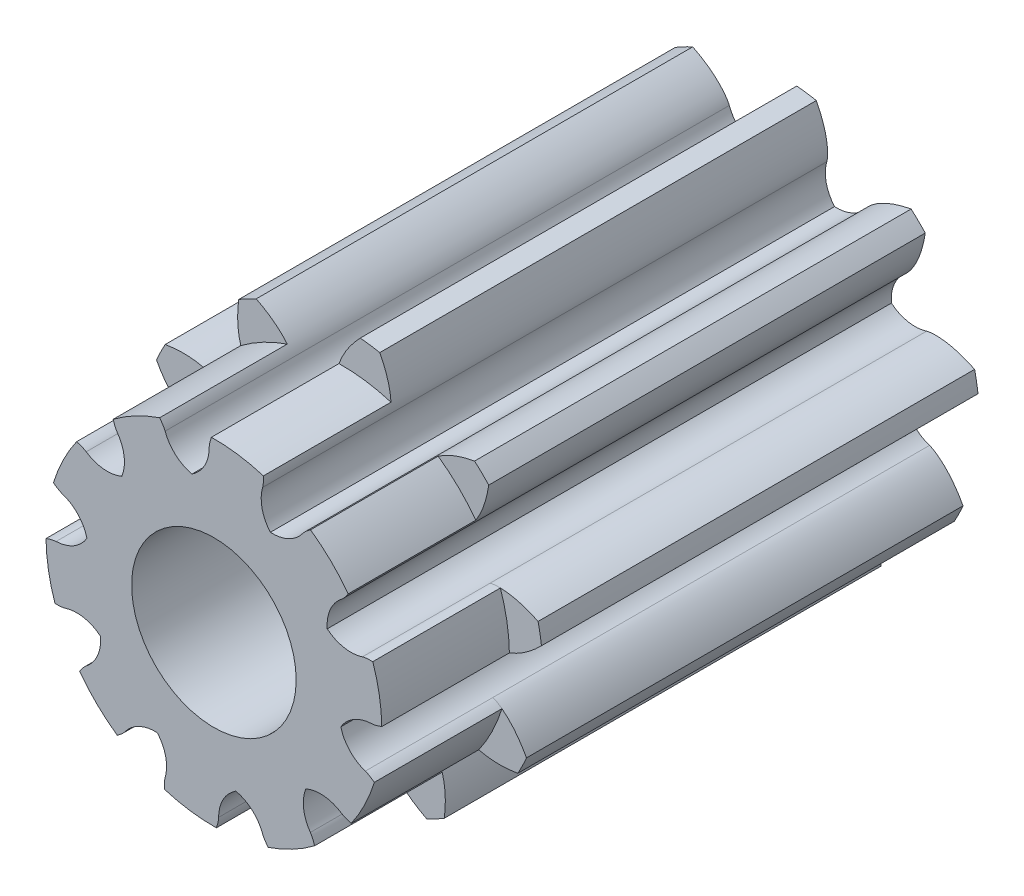
SolidWorks part; units mm, degrees
ref_plane "Front Plane" through (0, 0, 0) normal (0, 0, 1) x (1, 0, 0)
ref_plane "Top Plane" through (0, 0, 0) normal (0, 1, 0) x (1, 0, 0)
ref_plane "Right Plane" through (0, 0, 0) normal (1, 0, 0) x (0, 0, -1)
sketch "Sketch2" plane through (0, 0, 0) normal (0, 0, 1) x (1, 0, 0)
  spline S0 degree 4 poles (2.3492, 0) (2.3535, 0.0001) (2.3655, 0.001) (2.388, 0.0043) (2.4244, 0.0122) (2.4699, 0.0257) (2.5274, 0.0472) (2.5933, 0.0776) (2.6634, 0.116) (2.7368, 0.1632) (2.8072, 0.2147) (2.8746, 0.2702) (2.9391, 0.329) (3.0137, 0.4042) (3.0983, 0.4998) (3.1894, 0.6188) (3.2832, 0.7619) (3.368, 0.9153) (3.4422, 1.0722) (3.5063, 1.2365) (3.5603, 1.3995) (3.6047, 1.5733) (3.6397, 1.7361) (3.6656, 1.9222) (3.6825, 2.0736) (3.6905, 2.276) (3.6909, 2.3963) (3.6864, 2.5375) (3.6817, 2.6005) (3.679, 2.6392) knots 0 0 0 0 0 0.005377 0.015084 0.028532 0.04661 0.064855 0.092111 0.119476 0.146842 0.174209 0.201575 0.228941 0.256307 0.307035 0.361767 0.4165 0.471232 0.525964 0.580697 0.635429 0.690161 0.744894 0.799626 0.854358 0.909091 0.954545 1 1 1 1 1 construction
  spline S1 degree 4 poles (2.3492, 0) (2.3535, 0.0001) (2.3655, 0.001) (2.388, 0.0043) (2.4244, 0.0122) (2.4699, 0.0257) (2.5274, 0.0472) (2.5933, 0.0776) (2.6634, 0.116) (2.7368, 0.1632) (2.8072, 0.2147) (2.8746, 0.2702) (2.9391, 0.329) (3.0137, 0.4042) (3.0983, 0.4998) (3.1894, 0.6188) (3.2832, 0.7619) (3.368, 0.9153) (3.4422, 1.0722) (3.5063, 1.2365) (3.5603, 1.3995) (3.6047, 1.5733) (3.6397, 1.7361) (3.6656, 1.9222) (3.6825, 2.0736) (3.6888, 2.2322) (3.6902, 2.3096) (3.6902, 2.3492) knots 0 0 0 0 0 0.005377 0.015084 0.028532 0.04661 0.064855 0.092111 0.119476 0.146842 0.174209 0.201575 0.228941 0.256307 0.307035 0.361767 0.4165 0.471232 0.525964 0.580697 0.635429 0.690161 0.744894 0.799626 0.854358 0.909091 0.909091 0.909091 0.909091 0.909091
sketch "Sketch3" plane through (0, 0, 0) normal (0, 0, 1) x (1, 0, 0)
  line L0 (0, 0) -> (4.3237, 0) construction
  line L1 (3.6796, 0) -> (-3.6796, 0) construction
  line L2 (0, 0) -> (4.6983, 0.8161) construction
  circle A0 centre (0, 0) radius 2.3492 construction
  circle A1 centre (0, 0) radius 2.5 construction
  circle A2 centre (0, 0) radius 1.875
  circle A3 centre (0, 0) radius 3
  arc A4 (2.3492, 0) -> (1.8252, -0.4294) centre (2.3678, -0.5571) ccw
  arc A5 (2.2116, 0.7922) -> (1.5734, 1.0198) centre (2.0412, 1.323) cw
  spline S0 degree 4 poles (1.2598, 2999.6445) (0.5098, 35.997) (1.2863, 0.522) (1.9195, -0.0971) (2.4244, 0.0122) (2.4699, 0.0257) (2.5274, 0.0472) (2.5933, 0.0776) (2.6634, 0.116) (2.7368, 0.1632) (2.8072, 0.2147) (2.8746, 0.2702) (2.9391, 0.329) (3.0137, 0.4042) (3.0983, 0.4998) (3.1894, 0.6188) (3.2832, 0.7619) (3.368, 0.9153) (3.4422, 1.0722) (3.5063, 1.2365) (3.5603, 1.3995) (3.6047, 1.5733) (3.6397, 1.7361) (3.6656, 1.9222) (3.7713, 2.8662) (3.4608, 6.6353) (2.9119, -59.9143) (2.2294, 3002.2795) knots -0.601208 -0.601208 -0.601208 -0.601208 -0.601208 0.005377 0.015084 0.028532 0.04661 0.064855 0.092111 0.119476 0.146842 0.174209 0.201575 0.228941 0.256307 0.307035 0.361767 0.4165 0.471232 0.525964 0.580697 0.635429 0.690161 0.744894 0.799626 0.854358 2.055109 2.055109 2.055109 2.055109 2.055109 only from (2.3492, 0) to (3.6902, 2.3492) construction
  spline S1 degree 4 poles (2.3492, 0) (2.3535, 0.0001) (2.3655, 0.001) (2.388, 0.0043) (2.4244, 0.0122) (2.4699, 0.0257) (2.5274, 0.0472) (2.5933, 0.0776) (2.6634, 0.116) (2.7368, 0.1632) (2.8072, 0.2147) (2.8768, 0.272) (2.927, 0.318) (2.9601, 0.3506) (2.9773, 0.3681) knots 0 0 0 0 0 0.005377 0.015084 0.028532 0.04661 0.064855 0.092111 0.119476 0.146842 0.174209 0.201575 0.232398 0.232398 0.232398 0.232398 0.232398
  spline S2 degree 4 poles (2.2116, 0.7922) (2.2157, 0.7935) (2.2273, 0.7968) (2.2496, 0.8013) (2.2865, 0.8061) (2.3339, 0.8087) (2.3953, 0.8078) (2.4676, 0.8015) (2.5465, 0.7889) (2.6315, 0.7693) (2.7152, 0.7445) (2.8, 0.7141) (2.8628, 0.6877) (2.9049, 0.6682) (2.9271, 0.6575) knots 0 0 0 0 0 0.005377 0.015084 0.028532 0.04661 0.064855 0.092111 0.119476 0.146842 0.174209 0.201575 0.232398 0.232398 0.232398 0.232398 0.232398
  point P15 (2.4631, 0.4278)
  point P16 (2.4997, 0.0373)
  dimension "D1" = 6
  dimension "D2" = 3.75
  dimension "D3" = 5
  dimension "D4" = 4.6985
  dimension "D5" = 0.3927
extrude "Boss-Extrude1" add sketch "Sketch3" along normal blind 6.5 contours A2 region at (0, 0, 0)
extrude "Boss-Extrude2" add sketch "Sketch3<3>" along normal up to surface (6.5 mm away) contours S2 A5 A2 A4 S1 A3 region at (2.3064, 0.4006, 0) up to face at (1.875, 0, 6.5)
sketch "Sketch3<3>" plane through (0, 0, 0) normal (0, 0, 1) x (1, 0, 0) same geometry as "Sketch3"
pattern_circular "CirPattern1" count 10 over 360 about axis through (0, 0, 6.5) along (0, 0, -1) of "Boss-Extrude2"
sketch "Sketch4" plane through (0, 0, 6.5) normal (0, 0, 1) x (1, 0, 0)
  circle A0 centre (0, 0) radius 1.225
  dimension "D1" = 2.45
extrude "Cut-Extrude1" cut sketch "Sketch4" against normal blind 6.5
sketch "Sketch5" plane through (0, 0, 6.5) normal (0, 0, 1) x (1, 0, 0)
  circle A0 centre (0, 0) radius 1.225 construction
  circle A1 centre (0, 0) radius 1.225
  arc A2 (-0.8079, 2.3659) -> (-1.4994, 2.0004) centre (0, 0) ccw
  arc A3 (-2.0442, 1.4392) -> (-2.3889, 0.737) centre (0, 0) ccw
  arc A4 (-2.4997, -0.0373) -> (-2.3659, -0.8079) centre (0, 0) ccw
  arc A5 (-2.0004, -1.4994) -> (-1.4392, -2.0442) centre (0, 0) ccw
  arc A6 (-0.737, -2.3889) -> (0.0373, -2.4997) centre (0, 0) ccw
  arc A7 (0.8079, -2.3659) -> (1.4994, -2.0004) centre (0, 0) ccw
  arc A8 (2.0442, -1.4392) -> (2.3889, -0.737) centre (0, 0) ccw
  arc A9 (2.4997, 0.0373) -> (2.3659, 0.8079) centre (0, 0) ccw
  arc A10 (2.0004, 1.4994) -> (1.4392, 2.0442) centre (0, 0) ccw
  arc A11 (0.737, 2.3889) -> (-0.0373, 2.4997) centre (0, 0) ccw
  arc A30 (1.8897, -0.2705) -> (2.2549, -0.659) centre (2.429, -0.1295) ccw
  arc A31 (2.3492, 0) -> (1.8897, -0.2705) centre (2.3678, -0.5571) ccw
  arc A32 (2.9773, 0.3681) -> (2.9271, 0.6575) centre (0, 0) ccw
  arc A33 (1.6878, 0.8919) -> (2.2116, 0.7922) centre (2.0412, 1.323) ccw
  arc A34 (1.9006, 1.3808) -> (1.6878, 0.8919) centre (2.243, 0.941) ccw
  arc A35 (2.1923, 2.0478) -> (1.9816, 2.2524) centre (0, 0) ccw
  arc A36 (0.8412, 1.7136) -> (1.3236, 1.9409) centre (0.8737, 2.2701) ccw
  arc A37 (0.726, 2.2343) -> (0.8412, 1.7136) centre (1.2615, 2.0797) ccw
  arc A38 (0.57, 2.9454) -> (0.2792, 2.987) centre (0, 0) ccw
  arc A39 (-0.3267, 1.8808) -> (-0.07, 2.3482) centre (-0.6274, 2.3501) ccw
  arc A40 (-0.726, 2.2343) -> (-0.3267, 1.8808) centre (-0.2018, 2.424) ccw
  arc A41 (-1.2701, 2.7179) -> (-1.5298, 2.5806) centre (0, 0) ccw
  arc A42 (-1.3698, 1.3296) -> (-1.4369, 1.8586) centre (-1.889, 1.5325) ccw
  arc A43 (-1.9006, 1.3808) -> (-1.3698, 1.3296) centre (-1.5881, 1.8424) ccw
  arc A44 (-2.6251, 1.4522) -> (-2.7545, 1.1886) centre (0, 0) ccw
  arc A45 (-1.8897, 0.2705) -> (-2.2549, 0.659) centre (-2.429, 0.1295) ccw
  arc A46 (-2.3492, 0) -> (-1.8897, 0.2705) centre (-2.3678, 0.5571) ccw
  arc A47 (-2.9773, -0.3681) -> (-2.9271, -0.6575) centre (0, 0) ccw
  arc A48 (-1.6878, -0.8919) -> (-2.2116, -0.7922) centre (-2.0412, -1.323) ccw
  arc A49 (-1.9006, -1.3808) -> (-1.6878, -0.8919) centre (-2.243, -0.941) ccw
  arc A50 (-2.1923, -2.0478) -> (-1.9816, -2.2524) centre (0, 0) ccw
  arc A51 (-0.8412, -1.7136) -> (-1.3236, -1.9409) centre (-0.8737, -2.2701) ccw
  arc A52 (-0.726, -2.2343) -> (-0.8412, -1.7136) centre (-1.2615, -2.0797) ccw
  arc A53 (-0.57, -2.9454) -> (-0.2792, -2.987) centre (0, 0) ccw
  arc A54 (0.3267, -1.8808) -> (0.07, -2.3482) centre (0.6274, -2.3501) ccw
  arc A55 (0.726, -2.2343) -> (0.3267, -1.8808) centre (0.2018, -2.424) ccw
  arc A56 (1.2701, -2.7179) -> (1.5298, -2.5806) centre (0, 0) ccw
  arc A57 (1.3698, -1.3296) -> (1.4369, -1.8586) centre (1.889, -1.5325) ccw
  arc A58 (1.9006, -1.3808) -> (1.3698, -1.3296) centre (1.5881, -1.8424) ccw
  arc A59 (2.6251, -1.4522) -> (2.7545, -1.1886) centre (0, 0) ccw
  arc A60 (1.8897, -0.2705) -> (2.2549, -0.659) centre (2.429, -0.1295) ccw
  arc A61 (2.3492, 0) -> (1.8897, -0.2705) centre (2.3678, -0.5571) ccw
  arc A63 (1.6878, 0.8919) -> (2.2116, 0.7922) centre (2.0412, 1.323) ccw
  arc A64 (1.9006, 1.3808) -> (1.6878, 0.8919) centre (2.243, 0.941) ccw
  arc A66 (0.8412, 1.7136) -> (1.3236, 1.9409) centre (0.8737, 2.2701) ccw
  arc A67 (0.726, 2.2343) -> (0.8412, 1.7136) centre (1.2615, 2.0797) ccw
  arc A69 (-0.3267, 1.8808) -> (-0.07, 2.3482) centre (-0.6274, 2.3501) ccw
  arc A70 (-0.726, 2.2343) -> (-0.3267, 1.8808) centre (-0.2018, 2.424) ccw
  arc A72 (-1.3698, 1.3296) -> (-1.4369, 1.8586) centre (-1.889, 1.5325) ccw
  arc A73 (-1.9006, 1.3808) -> (-1.3698, 1.3296) centre (-1.5881, 1.8424) ccw
  arc A75 (-1.8897, 0.2705) -> (-2.2549, 0.659) centre (-2.429, 0.1295) ccw
  arc A76 (-2.3492, 0) -> (-1.8897, 0.2705) centre (-2.3678, 0.5571) ccw
  arc A78 (-1.6878, -0.8919) -> (-2.2116, -0.7922) centre (-2.0412, -1.323) ccw
  arc A79 (-1.9006, -1.3808) -> (-1.6878, -0.8919) centre (-2.243, -0.941) ccw
  arc A81 (-0.8412, -1.7136) -> (-1.3236, -1.9409) centre (-0.8737, -2.2701) ccw
  arc A82 (-0.726, -2.2343) -> (-0.8412, -1.7136) centre (-1.2615, -2.0797) ccw
  arc A84 (0.3267, -1.8808) -> (0.07, -2.3482) centre (0.6274, -2.3501) ccw
  arc A85 (0.726, -2.2343) -> (0.3267, -1.8808) centre (0.2018, -2.424) ccw
  arc A87 (1.3698, -1.3296) -> (1.4369, -1.8586) centre (1.889, -1.5325) ccw
  arc A88 (1.9006, -1.3808) -> (1.3698, -1.3296) centre (1.5881, -1.8424) ccw
  spline S20 degree 4 poles (1.2598, 2999.7738) (0.5098, 35.9981) (1.2863, 0.522) (1.9194, -0.0971) (2.4244, 0.0122) (2.4699, 0.0257) (2.5274, 0.0472) (2.5933, 0.0776) (2.6634, 0.116) (2.7368, 0.1632) (2.8072, 0.2147) (4.8119, 1.8647) (3.3546, 7.3675) (1.052, 5.6298) (-1.6472, -2999.6052) knots -0.601214 -0.601214 -0.601214 -0.601214 -0.601214 0.005377 0.015084 0.028532 0.04661 0.064855 0.092111 0.119476 0.146842 0.174209 0.201575 3.374744 3.374744 3.374744 3.374744 3.374744 only from (2.3492, 0) to (2.9773, 0.3681)
  spline S21 degree 4 poles (-1013.0696, 2823.2643) (2.8889, -4.9453) (5.6426, -5.8046) (5.1589, -0.1327) (2.7152, 0.7445) (2.6315, 0.7693) (2.5465, 0.7889) (2.4676, 0.8015) (2.3953, 0.8078) (2.3339, 0.8087) (2.2865, 0.8061) (1.7743, 0.7387) (1.387, -0.0576) (12.6186, -33.7149) (1012.6847, -2823.3385) knots -3.142323 -3.142323 -3.142323 -3.142323 -3.142323 0.030823 0.05819 0.085556 0.112922 0.140288 0.167544 0.185788 0.203867 0.217315 0.227022 0.833597 0.833597 0.833597 0.833597 0.833597 only from (2.9271, 0.6575) to (2.2116, 0.7922)
  spline S22 degree 4 poles (-1762.2036, 2427.6085) (-20.7467, 29.4227) (0.7338, 1.1784) (1.6099, 1.0497) (1.9542, 1.4349) (1.983, 1.4726) (2.0169, 1.5238) (2.0524, 1.5871) (2.0865, 1.6594) (2.1182, 1.7406) (2.1449, 1.8238) (2.7969, 4.3369) (-1.6166, 7.9322) (-2.458, 5.173) (1761.7911, -2427.6998) knots -0.601214 -0.601214 -0.601214 -0.601214 -0.601214 0.005377 0.015084 0.028532 0.04661 0.064855 0.092111 0.119476 0.146842 0.174209 0.201575 3.374744 3.374744 3.374744 3.374744 3.374744 only from (1.9006, 1.3808) to (2.1923, 2.0478)
  spline S23 degree 4 poles (-2479.0637, 1688.6014) (5.244, -2.3027) (7.9768, -1.3794) (4.2516, 2.9249) (1.759, 2.1983) (1.6767, 2.1692) (1.5964, 2.1351) (1.5252, 2.0988) (1.463, 2.0615) (1.4128, 2.026) (1.376, 1.9961) (1.0012, 1.6405) (1.156, 0.7686) (30.0258, -19.8589) (2478.7959, -1688.8877) knots -3.142323 -3.142323 -3.142323 -3.142323 -3.142323 0.030823 0.05819 0.085556 0.112922 0.140288 0.167544 0.185788 0.203867 0.217315 0.227022 0.833597 0.833597 0.833597 0.833597 0.833597 only from (1.9816, 2.2524) to (1.3236, 1.9409)
  spline S24 degree 4 poles (-2852.5651, 928.1792) (-34.0787, 11.6089) (-0.099, 1.3847) (0.6855, 1.7955) (0.7376, 2.3095) (0.7388, 2.3569) (0.7361, 2.4183) (0.7276, 2.4903) (0.7127, 2.5689) (0.6905, 2.6533) (0.6633, 2.7362) (-0.2864, 5.1527) (-5.9703, 5.467) (-5.0292, 2.7402) (2852.2851, -928.4956) knots -0.601214 -0.601214 -0.601214 -0.601214 -0.601214 0.005377 0.015084 0.028532 0.04661 0.064855 0.092111 0.119476 0.146842 0.174209 0.201575 3.374744 3.374744 3.374744 3.374744 3.374744 only from (0.726, 2.2343) to (0.57, 2.9454)
  spline S25 degree 4 poles (-2998.1397, -91.0498) (5.596, 1.2194) (7.2641, 3.5727) (1.7204, 4.8654) (0.131, 2.8124) (0.0815, 2.7404) (0.0366, 2.6657) (0.0002, 2.5945) (-0.0281, 2.5277) (-0.0479, 2.4695) (-0.0601, 2.4237) (-0.1543, 1.9157) (0.4834, 1.3013) (35.9641, 1.5825) (2998.0912, 90.6608) knots -3.142323 -3.142323 -3.142323 -3.142323 -3.142323 0.030823 0.05819 0.085556 0.112922 0.140288 0.167544 0.185788 0.203867 0.217315 0.227022 0.833597 0.833597 0.833597 0.833597 0.833597 only from (0.2792, 2.987) to (-0.07, 2.3482)
  spline S26 degree 4 poles (-2853.3437, -925.7829) (-34.3938, -10.6392) (-0.894, 1.062) (-0.5008, 1.8555) (-0.7607, 2.302) (-0.7877, 2.341) (-0.8259, 2.3891) (-0.8752, 2.4424) (-0.9334, 2.4972) (-1.0009, 2.5524) (-1.0717, 2.6035) (-3.2604, 4.0002) (-8.0435, 0.9137) (-5.6793, -0.7392) (2853.3031, 925.3624) knots -0.601214 -0.601214 -0.601214 -0.601214 -0.601214 0.005377 0.015084 0.028532 0.04661 0.064855 0.092111 0.119476 0.146842 0.174209 0.201575 3.374744 3.374744 3.374744 3.374744 3.374744 only from (-0.726, 2.2343) to (-1.2701, 2.7179)
  spline S27 degree 4 poles (-2372.0282, -1835.9231) (3.8105, 4.2757) (3.7768, 7.1601) (-1.468, 4.9474) (-1.5471, 2.3522) (-1.5448, 2.265) (-1.5372, 2.1781) (-1.5248, 2.0991) (-1.5085, 2.0284) (-1.4903, 1.9697) (-1.4732, 1.9255) (-1.2508, 1.4592) (-0.3738, 1.3369) (28.1654, 22.4195) (2372.2177, 1835.58) knots -3.142323 -3.142323 -3.142323 -3.142323 -3.142323 0.030823 0.05819 0.085556 0.112922 0.140288 0.167544 0.185788 0.203867 0.217315 0.227022 0.833597 0.833597 0.833597 0.833597 0.833597 only from (-1.5298, 2.5806) to (-1.4369, 1.8586)
  spline S28 degree 4 poles (-1764.242, -2426.1275) (-21.5716, -28.8234) (-1.3475, 0.3337) (-1.4958, 1.2068) (-1.9685, 1.4152) (-2.0133, 1.4309) (-2.0725, 1.4474) (-2.1436, 1.4615) (-2.2229, 1.4716) (-2.31, 1.4766) (-2.3973, 1.4763) (-4.989, 1.3198) (-7.0444, -3.9887) (-4.1602, -3.9363) (1764.4563, 2425.7634) knots -0.601214 -0.601214 -0.601214 -0.601214 -0.601214 0.005377 0.015084 0.028532 0.04661 0.064855 0.092111 0.119476 0.146842 0.174209 0.201575 3.374744 3.374744 3.374744 3.374744 3.374744 only from (-1.9006, 1.3808) to (-2.6251, 1.4522)
  spline S29 degree 4 poles (-839.8826, -2879.5362) (0.5696, 5.6989) (-1.1531, 8.0126) (-4.0956, 3.1397) (-2.6343, 0.9936) (-2.5811, 0.9244) (-2.5239, 0.8585) (-2.4674, 0.802) (-2.4127, 0.7544) (-2.3635, 0.7176) (-2.3236, 0.6918) (-1.8696, 0.4453) (-1.0882, 0.8619) (9.6085, 34.693) (840.2376, 2879.3699) knots -3.142323 -3.142323 -3.142323 -3.142323 -3.142323 0.030823 0.05819 0.085556 0.112922 0.140288 0.167544 0.185788 0.203867 0.217315 0.227022 0.833597 0.833597 0.833597 0.833597 0.833597 only from (-2.7545, 1.1886) to (-2.2549, 0.659)
  spline S30 degree 4 poles (-1.2598, -2999.7738) (-0.5098, -35.9981) (-1.2863, -0.522) (-1.9194, 0.0971) (-2.4244, -0.0122) (-2.4699, -0.0257) (-2.5274, -0.0472) (-2.5933, -0.0776) (-2.6634, -0.116) (-2.7368, -0.1632) (-2.8072, -0.2147) (-4.8119, -1.8647) (-3.3546, -7.3675) (-1.052, -5.6298) (1.6472, 2999.6052) knots -0.601214 -0.601214 -0.601214 -0.601214 -0.601214 0.005377 0.015084 0.028532 0.04661 0.064855 0.092111 0.119476 0.146842 0.174209 0.201575 3.374744 3.374744 3.374744 3.374744 3.374744 only from (-2.3492, 0) to (-2.9773, -0.3681)
  spline S31 degree 4 poles (1013.0696, -2823.2643) (-2.8889, 4.9453) (-5.6426, 5.8046) (-5.1589, 0.1327) (-2.7152, -0.7445) (-2.6315, -0.7693) (-2.5465, -0.7889) (-2.4676, -0.8015) (-2.3953, -0.8078) (-2.3339, -0.8087) (-2.2865, -0.8061) (-1.7743, -0.7387) (-1.387, 0.0576) (-12.6186, 33.7149) (-1012.6847, 2823.3385) knots -3.142323 -3.142323 -3.142323 -3.142323 -3.142323 0.030823 0.05819 0.085556 0.112922 0.140288 0.167544 0.185788 0.203867 0.217315 0.227022 0.833597 0.833597 0.833597 0.833597 0.833597 only from (-2.9271, -0.6575) to (-2.2116, -0.7922)
  spline S32 degree 4 poles (1762.2036, -2427.6085) (20.7467, -29.4227) (-0.7338, -1.1784) (-1.6099, -1.0497) (-1.9542, -1.4349) (-1.983, -1.4726) (-2.0169, -1.5238) (-2.0524, -1.5871) (-2.0865, -1.6594) (-2.1182, -1.7406) (-2.1449, -1.8238) (-2.7969, -4.3369) (1.6166, -7.9322) (2.458, -5.173) (-1761.7911, 2427.6998) knots -0.601214 -0.601214 -0.601214 -0.601214 -0.601214 0.005377 0.015084 0.028532 0.04661 0.064855 0.092111 0.119476 0.146842 0.174209 0.201575 3.374744 3.374744 3.374744 3.374744 3.374744 only from (-1.9006, -1.3808) to (-2.1923, -2.0478)
  spline S33 degree 4 poles (2479.0637, -1688.6014) (-5.244, 2.3027) (-7.9768, 1.3794) (-4.2516, -2.9249) (-1.759, -2.1983) (-1.6767, -2.1692) (-1.5964, -2.1351) (-1.5252, -2.0988) (-1.463, -2.0615) (-1.4128, -2.026) (-1.376, -1.9961) (-1.0012, -1.6405) (-1.156, -0.7686) (-30.0258, 19.8589) (-2478.7959, 1688.8877) knots -3.142323 -3.142323 -3.142323 -3.142323 -3.142323 0.030823 0.05819 0.085556 0.112922 0.140288 0.167544 0.185788 0.203867 0.217315 0.227022 0.833597 0.833597 0.833597 0.833597 0.833597 only from (-1.9816, -2.2524) to (-1.3236, -1.9409)
  spline S34 degree 4 poles (2852.5651, -928.1792) (34.0787, -11.6089) (0.099, -1.3847) (-0.6855, -1.7955) (-0.7376, -2.3095) (-0.7388, -2.3569) (-0.7361, -2.4183) (-0.7276, -2.4903) (-0.7127, -2.5689) (-0.6905, -2.6533) (-0.6633, -2.7362) (0.2864, -5.1527) (5.9703, -5.467) (5.0292, -2.7402) (-2852.2851, 928.4955) knots -0.601214 -0.601214 -0.601214 -0.601214 -0.601214 0.005377 0.015084 0.028532 0.04661 0.064855 0.092111 0.119476 0.146842 0.174209 0.201575 3.374744 3.374744 3.374744 3.374744 3.374744 only from (-0.726, -2.2343) to (-0.57, -2.9454)
  spline S35 degree 4 poles (2998.1397, 91.0498) (-5.596, -1.2194) (-7.2641, -3.5727) (-1.7204, -4.8654) (-0.131, -2.8124) (-0.0815, -2.7404) (-0.0366, -2.6657) (-0.0002, -2.5945) (0.0281, -2.5277) (0.0479, -2.4695) (0.0601, -2.4237) (0.1543, -1.9157) (-0.4834, -1.3013) (-35.9641, -1.5825) (-2998.0912, -90.6608) knots -3.142323 -3.142323 -3.142323 -3.142323 -3.142323 0.030823 0.05819 0.085556 0.112922 0.140288 0.167544 0.185788 0.203867 0.217315 0.227022 0.833597 0.833597 0.833597 0.833597 0.833597 only from (-0.2792, -2.987) to (0.07, -2.3482)
  spline S36 degree 4 poles (2853.3437, 925.7829) (34.3938, 10.6392) (0.894, -1.062) (0.5008, -1.8555) (0.7607, -2.302) (0.7877, -2.341) (0.8259, -2.3891) (0.8752, -2.4424) (0.9334, -2.4972) (1.0009, -2.5524) (1.0717, -2.6035) (3.2604, -4.0002) (8.0435, -0.9137) (5.6793, 0.7392) (-2853.3031, -925.3624) knots -0.601214 -0.601214 -0.601214 -0.601214 -0.601214 0.005377 0.015084 0.028532 0.04661 0.064855 0.092111 0.119476 0.146842 0.174209 0.201575 3.374744 3.374744 3.374744 3.374744 3.374744 only from (0.726, -2.2343) to (1.2701, -2.7179)
  spline S37 degree 4 poles (2372.0282, 1835.9231) (-3.8105, -4.2757) (-3.7768, -7.1601) (1.468, -4.9474) (1.5471, -2.3522) (1.5448, -2.265) (1.5372, -2.1781) (1.5248, -2.0991) (1.5085, -2.0284) (1.4903, -1.9697) (1.4732, -1.9255) (1.2508, -1.4592) (0.3738, -1.3369) (-28.1654, -22.4195) (-2372.2177, -1835.58) knots -3.142323 -3.142323 -3.142323 -3.142323 -3.142323 0.030823 0.05819 0.085556 0.112922 0.140288 0.167544 0.185788 0.203867 0.217315 0.227022 0.833597 0.833597 0.833597 0.833597 0.833597 only from (1.5298, -2.5806) to (1.4369, -1.8586)
  spline S38 degree 4 poles (1764.242, 2426.1275) (21.5716, 28.8234) (1.3475, -0.3337) (1.4958, -1.2068) (1.9685, -1.4152) (2.0133, -1.4309) (2.0725, -1.4474) (2.1436, -1.4615) (2.2229, -1.4716) (2.31, -1.4766) (2.3973, -1.4763) (4.989, -1.3198) (7.0444, 3.9887) (4.1602, 3.9363) (-1764.4563, -2425.7634) knots -0.601214 -0.601214 -0.601214 -0.601214 -0.601214 0.005377 0.015084 0.028532 0.04661 0.064855 0.092111 0.119476 0.146842 0.174209 0.201575 3.374744 3.374744 3.374744 3.374744 3.374744 only from (1.9006, -1.3808) to (2.6251, -1.4522)
  spline S39 degree 4 poles (839.8826, 2879.5362) (-0.5696, -5.6989) (1.1531, -8.0126) (4.0956, -3.1397) (2.6343, -0.9936) (2.5811, -0.9244) (2.5239, -0.8585) (2.4674, -0.802) (2.4127, -0.7544) (2.3635, -0.7176) (2.3236, -0.6918) (1.8696, -0.4453) (1.0882, -0.8619) (-9.6085, -34.693) (-840.2376, -2879.3699) knots -3.142323 -3.142323 -3.142323 -3.142323 -3.142323 0.030823 0.05819 0.085556 0.112922 0.140288 0.167544 0.185788 0.203867 0.217315 0.227022 0.833597 0.833597 0.833597 0.833597 0.833597 only from (2.7545, -1.1886) to (2.2549, -0.659)
  spline S40 degree 4 poles (2.3492, 0) (2.3535, 0.0001) (2.3655, 0.001) (2.388, 0.0043) (2.4261, 0.0125) (2.4593, 0.0226) (2.4846, 0.0315) (2.4997, 0.0373) knots 0 0 0 0 0 0.005377 0.015084 0.028532 0.048809 0.048809 0.048809 0.048809 0.048809
  spline S41 degree 4 poles (2.3659, 0.8079) (2.3497, 0.8082) (2.3228, 0.8081) (2.2882, 0.8063) (2.2496, 0.8013) (2.2273, 0.7968) (2.2157, 0.7935) (2.2116, 0.7922) knots 0.18359 0.18359 0.18359 0.18359 0.18359 0.203867 0.217315 0.227022 0.232398 0.232398 0.232398 0.232398 0.232398
  spline S42 degree 4 poles (1.9006, 1.3808) (1.904, 1.3835) (1.9132, 1.3912) (1.9294, 1.4071) (1.9554, 1.4362) (1.9763, 1.4638) (1.9916, 1.4859) (2.0004, 1.4994) knots 0 0 0 0 0 0.005377 0.015084 0.028532 0.048809 0.048809 0.048809 0.048809 0.048809
  spline S43 degree 4 poles (1.4392, 2.0442) (1.4259, 2.035) (1.4042, 2.0191) (1.3772, 1.9973) (1.349, 1.9705) (1.3336, 1.9538) (1.3261, 1.9443) (1.3236, 1.9409) knots 0.18359 0.18359 0.18359 0.18359 0.18359 0.203867 0.217315 0.227022 0.232398 0.232398 0.232398 0.232398 0.232398
  spline S44 degree 4 poles (0.726, 2.2343) (0.7271, 2.2384) (0.73, 2.25) (0.7338, 2.2725) (0.7378, 2.3112) (0.7385, 2.3459) (0.7378, 2.3728) (0.737, 2.3889) knots 0 0 0 0 0 0.005377 0.015084 0.028532 0.048809 0.048809 0.048809 0.048809 0.048809
  spline S45 degree 4 poles (-0.0373, 2.4997) (-0.0426, 2.4845) (-0.0507, 2.4588) (-0.0598, 2.4254) (-0.0669, 2.3871) (-0.0695, 2.3645) (-0.07, 2.3525) (-0.07, 2.3482) knots 0.18359 0.18359 0.18359 0.18359 0.18359 0.203867 0.217315 0.227022 0.232398 0.232398 0.232398 0.232398 0.232398
  spline S46 degree 4 poles (-0.726, 2.2343) (-0.7274, 2.2383) (-0.7319, 2.2494) (-0.742, 2.2698) (-0.7616, 2.3035) (-0.7814, 2.3319) (-0.7978, 2.3533) (-0.8079, 2.3659) knots 0 0 0 0 0 0.005377 0.015084 0.028532 0.048809 0.048809 0.048809 0.048809 0.048809
  spline S47 degree 4 poles (-1.4994, 2.0004) (-1.4948, 1.985) (-1.4863, 1.9594) (-1.474, 1.927) (-1.4572, 1.8919) (-1.4461, 1.872) (-1.4394, 1.862) (-1.4369, 1.8586) knots 0.18359 0.18359 0.18359 0.18359 0.18359 0.203867 0.217315 0.227022 0.232398 0.232398 0.232398 0.232398 0.232398
  spline S48 degree 4 poles (-1.9006, 1.3808) (-1.9041, 1.3832) (-1.9143, 1.3896) (-1.9345, 1.4002) (-1.9701, 1.4159) (-2.0029, 1.4273) (-2.0286, 1.4349) (-2.0442, 1.4392) knots 0 0 0 0 0 0.005377 0.015084 0.028532 0.048809 0.048809 0.048809 0.048809 0.048809
  spline S49 degree 4 poles (-2.3889, 0.737) (-2.376, 0.7273) (-2.3542, 0.7116) (-2.3251, 0.6926) (-2.2909, 0.6741) (-2.2702, 0.6645) (-2.259, 0.6604) (-2.2549, 0.659) knots 0.18359 0.18359 0.18359 0.18359 0.18359 0.203867 0.217315 0.227022 0.232398 0.232398 0.232398 0.232398 0.232398
  spline S50 degree 4 poles (-2.3492, 0) (-2.3535, -0.0001) (-2.3655, -0.001) (-2.388, -0.0043) (-2.4261, -0.0125) (-2.4593, -0.0226) (-2.4846, -0.0315) (-2.4997, -0.0373) knots 0 0 0 0 0 0.005377 0.015084 0.028532 0.048809 0.048809 0.048809 0.048809 0.048809
  spline S51 degree 4 poles (-2.3659, -0.8079) (-2.3497, -0.8082) (-2.3228, -0.8081) (-2.2882, -0.8063) (-2.2496, -0.8013) (-2.2273, -0.7968) (-2.2157, -0.7935) (-2.2116, -0.7922) knots 0.18359 0.18359 0.18359 0.18359 0.18359 0.203867 0.217315 0.227022 0.232398 0.232398 0.232398 0.232398 0.232398
  spline S52 degree 4 poles (-1.9006, -1.3808) (-1.904, -1.3835) (-1.9132, -1.3912) (-1.9294, -1.4071) (-1.9554, -1.4362) (-1.9763, -1.4638) (-1.9916, -1.4859) (-2.0004, -1.4994) knots 0 0 0 0 0 0.005377 0.015084 0.028532 0.048809 0.048809 0.048809 0.048809 0.048809
  spline S53 degree 4 poles (-1.4392, -2.0442) (-1.4259, -2.035) (-1.4042, -2.0191) (-1.3772, -1.9973) (-1.349, -1.9705) (-1.3336, -1.9538) (-1.3261, -1.9443) (-1.3236, -1.9409) knots 0.18359 0.18359 0.18359 0.18359 0.18359 0.203867 0.217315 0.227022 0.232398 0.232398 0.232398 0.232398 0.232398
  spline S54 degree 4 poles (-0.726, -2.2343) (-0.7271, -2.2384) (-0.73, -2.25) (-0.7338, -2.2725) (-0.7378, -2.3112) (-0.7385, -2.3459) (-0.7378, -2.3728) (-0.737, -2.3889) knots 0 0 0 0 0 0.005377 0.015084 0.028532 0.048809 0.048809 0.048809 0.048809 0.048809
  spline S55 degree 4 poles (0.0373, -2.4997) (0.0426, -2.4845) (0.0507, -2.4588) (0.0598, -2.4254) (0.0669, -2.3871) (0.0695, -2.3645) (0.07, -2.3525) (0.07, -2.3482) knots 0.18359 0.18359 0.18359 0.18359 0.18359 0.203867 0.217315 0.227022 0.232398 0.232398 0.232398 0.232398 0.232398
  spline S56 degree 4 poles (0.726, -2.2343) (0.7274, -2.2383) (0.7319, -2.2494) (0.742, -2.2698) (0.7616, -2.3035) (0.7814, -2.3319) (0.7978, -2.3533) (0.8079, -2.3659) knots 0 0 0 0 0 0.005377 0.015084 0.028532 0.048809 0.048809 0.048809 0.048809 0.048809
  spline S57 degree 4 poles (1.4994, -2.0004) (1.4948, -1.985) (1.4863, -1.9594) (1.474, -1.927) (1.4572, -1.8919) (1.4461, -1.872) (1.4394, -1.862) (1.4369, -1.8586) knots 0.18359 0.18359 0.18359 0.18359 0.18359 0.203867 0.217315 0.227022 0.232398 0.232398 0.232398 0.232398 0.232398
  spline S58 degree 4 poles (1.9006, -1.3808) (1.9041, -1.3832) (1.9143, -1.3896) (1.9345, -1.4002) (1.9701, -1.4159) (2.0029, -1.4273) (2.0286, -1.4349) (2.0442, -1.4392) knots 0 0 0 0 0 0.005377 0.015084 0.028532 0.048809 0.048809 0.048809 0.048809 0.048809
  spline S59 degree 4 poles (2.3889, -0.737) (2.376, -0.7273) (2.3542, -0.7116) (2.3251, -0.6926) (2.2909, -0.6741) (2.2702, -0.6645) (2.259, -0.6604) (2.2549, -0.659) knots 0.18359 0.18359 0.18359 0.18359 0.18359 0.203867 0.217315 0.227022 0.232398 0.232398 0.232398 0.232398 0.232398
  dimension "D2" = 5
  dimension "D1" = 0
extrude "Boss-Extrude3" add sketch "Sketch5" along normal blind 1.9
equation "\"m\"= 22.5 / 45mm'module"
equation "\"N\"= 10'number of teeth"
equation "\"a\"= 20deg'pressure angle"
equation "\"da\"= \"m\" * ( \"N\" + 2 )'addendum circle diameter"
equation "\"df\"= \"m\" * ( \"N\" - 2.5 )'dedendum circle diameter"
equation "\"db\"= \"m\" * \"N\" * cos ( \"a\" )'basic circle diameter"
equation "\"rb\"= \"db\" / 2'basic circle radius"
equation "\"s\"= \"m\" * pi / 2'pitch circle tooth thickness"
equation "\"r\"= \"m\" * 0.38'dedendum circle angle"
equation "\"B\"= \"d\" * 0.3'tooth width"
equation "\"d\"= 5mm"
equation "\"D1@Sketch3\"=\"da\""
equation "\"D2@Sketch3\"=\"df\""
equation "\"D4@Sketch3\"=\"db\""
equation "\"D3@Sketch3\"=\"d\""
equation "\"D5@Sketch3\"=\"s\"/2"
